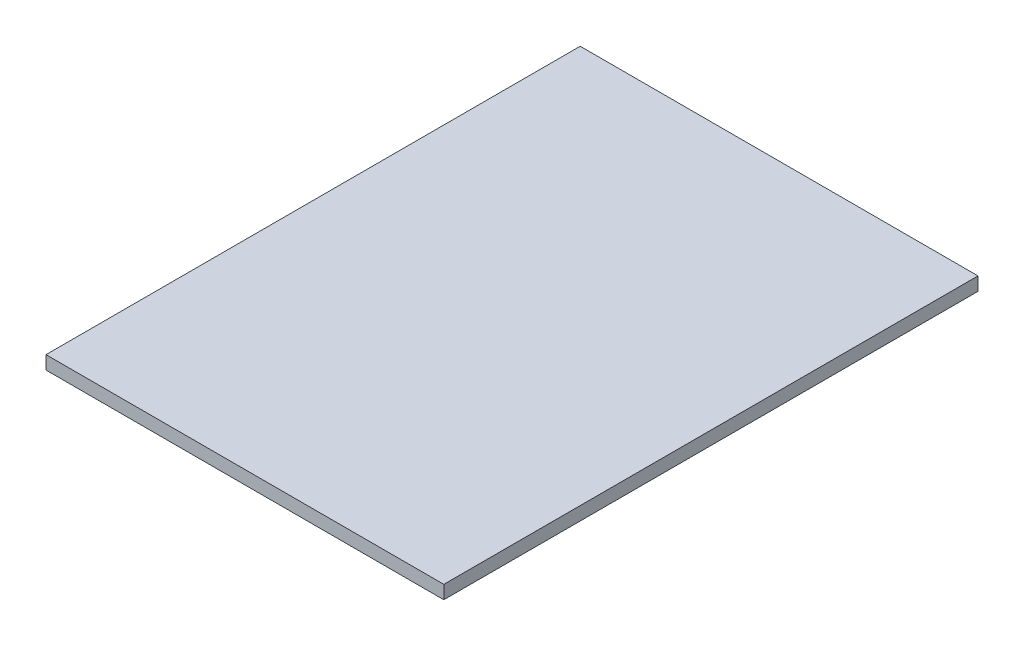
SolidWorks part; units mm, degrees
ref_plane "Front Plane" through (0, 0, 0) normal (0, 0, 1) x (1, 0, 0)
ref_plane "Top Plane" through (0, 0, 0) normal (0, 1, 0) x (1, 0, 0)
ref_plane "Right Plane" through (0, 0, 0) normal (1, 0, 0) x (0, 0, -1)
sketch "Sketch1" plane through (0, 0, 0) normal (0, 1, 0) x (1, 0, 0)
  line L1 (0, 0) -> (297.5, 0)
  line L2 (0, 0) -> (0, 399.5)
  line L3 (0, 399.5) -> (297.5, 399.5)
  line L4 (297.5, 0) -> (297.5, 399.5)
  dimension "D1" = 399.5
  dimension "D2" = 297.5
extrude "Boss-Extrude1" add sketch "Sketch1" along normal blind 10
